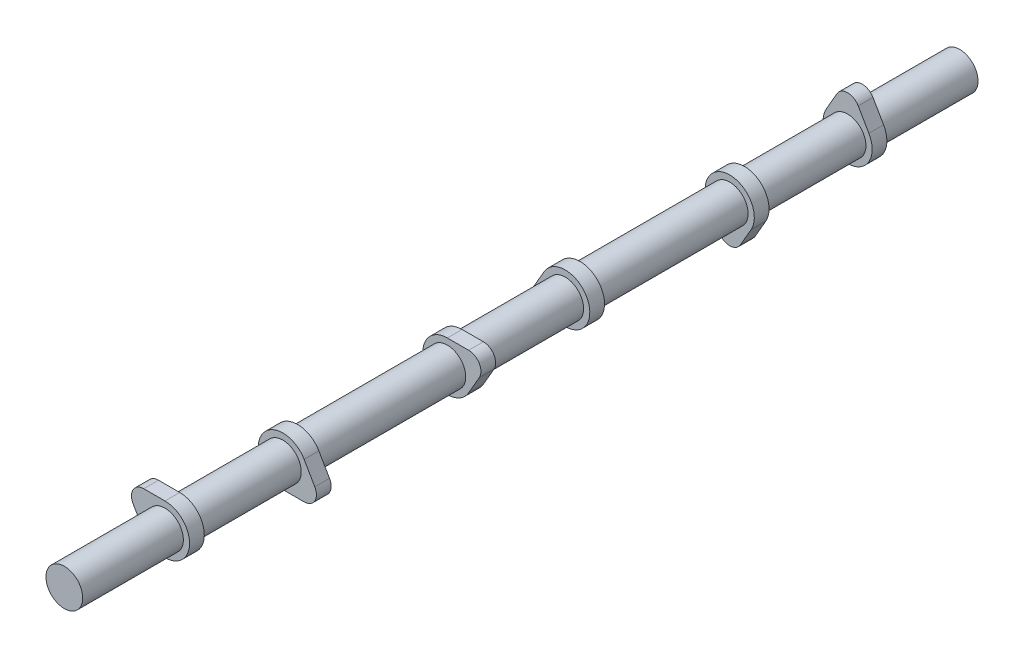
SolidWorks part; units mm, degrees
material "Plain Carbon Steel"
ref_plane "Front Plane" through (0, 0, 0) normal (0, 0, 1) x (1, 0, 0)
ref_plane "Top Plane" through (0, 0, 0) normal (0, 1, 0) x (1, 0, 0)
ref_plane "Right Plane" through (0, 0, 0) normal (1, 0, 0) x (0, 0, -1)
sketch "Sketch1" plane through (0, 0, 0) normal (0, 0, 1) x (1, 0, 0)
  line L0 (-5.4993, 15.875) -> (-10.9985, 6.35)
  line L1 (5.4993, 15.875) -> (10.9985, 6.35)
  arc A0 (-10.9985, 6.35) -> (10.9985, 6.35) centre (0, 0) ccw
  arc A1 (5.4993, 15.875) -> (-5.4993, 15.875) centre (0, 12.7) ccw
  dimension "D1" = 25.4
  dimension "D2" = 12.7
extrude "Boss-Extrude1" add sketch "Sketch1" along normal blind 7.62
ref_axis "Axis1" through (0, 0, 475.8644) along (0, 0, -1)
move or copy body "Body-Move/Copy1" bodies to move or copy 101 copy yes number of copies 1 translate (0, 0, 60.96)
move or copy body "Body-Move/Copy2" bodies to move or copy 102 copy no rotation origin (0, 0, 0) rotation axis (0, 0, 1) rotation angle 180
sketch "Sketch2" plane through (0, 0, 0) normal (0, 0, 1) x (1, 0, 0)
  circle A0 centre (0, 0) radius 9.5
  dimension "D1" = 19
extrude "Boss-Extrude2" add sketch "Sketch2" along normal blind 146.05 from offset 25.4 offset against normal yes
pattern_linear "LPattern1" count 3 spacing 146.05 along (0, 0, 1) of bodies 104
move or copy body "Body-Move/Copy3" bodies to move or copy 105 copy no rotation origin (0, 0, 0) rotation axis (0, 0, 1) rotation angle 120
move or copy body "Body-Move/Copy4" bodies to move or copy 106 copy no rotation origin (0, 0, 0) rotation axis (0, 0, -1) rotation angle 120
sketch "Sketch3" plane through (0, 0, -25.4) normal (0, 0, -1) x (-1, 0, 0)
  circle A1 centre (0, 0) radius 9.5
  circle A2 centre (0, 0) radius 9.5
  dimension "D1" = 0
extrude "Boss-Extrude3" add sketch "Sketch3" along normal blind 24.94
combine bodies "Combine1" operation type add bodies to combine 108 107 109
